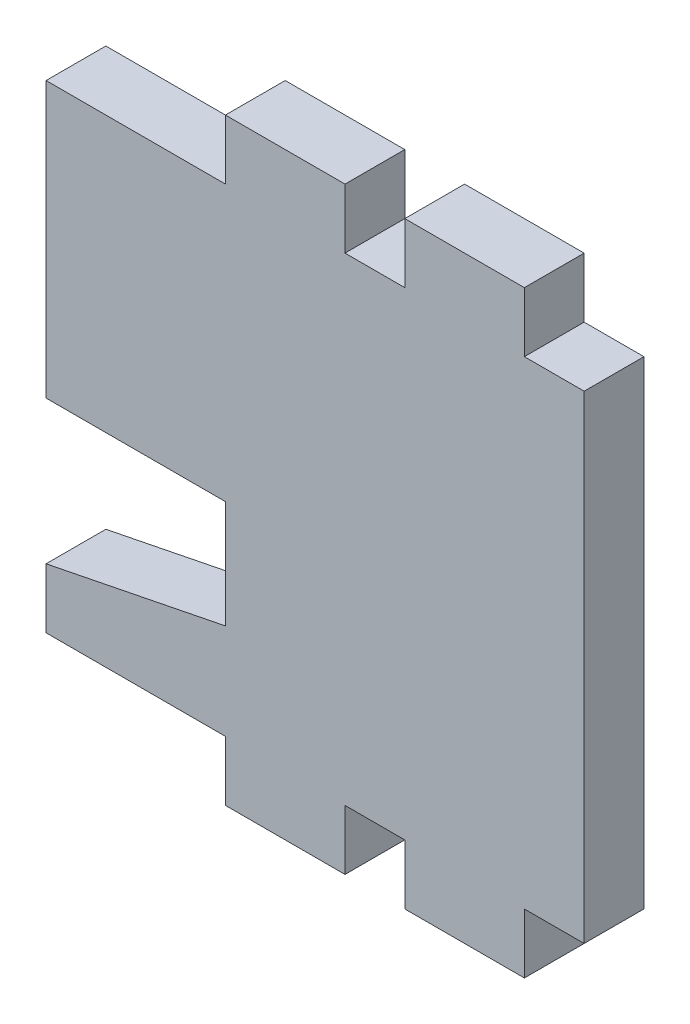
SolidWorks part; units mm, degrees
ref_plane "Plan de face" through (0, 0, 0) normal (0, 0, 1) x (1, 0, 0)
ref_plane "Plan de dessus" through (0, 0, 0) normal (0, 1, 0) x (1, 0, 0)
ref_plane "Plan de droite" through (0, 0, 0) normal (1, 0, 0) x (0, 0, -1)
sketch "Esquisse1" plane through (0, 0, 0) normal (0, 0, 1) x (1, 0, 0)
  line L0 (0, 20) -> (30, 20) construction
  line L1 (10, 0) -> (15, 0)
  line L2 (0, 0) -> (0, 40)
  line L3 (10, 40) -> (15, 40)
  line L4 (30, 0) -> (30, 40)
  line L5 (25, 40) -> (30, 40)
  line L6 (0, 40) -> (0, 45)
  line L7 (0, 45) -> (10, 45)
  line L8 (10, 40) -> (10, 45)
  line L9 (25, 0) -> (30, 0)
  line L10 (15, 40) -> (15, 45)
  line L11 (15, 45) -> (25, 45)
  line L12 (25, 40) -> (25, 45)
  line L13 (25, 0) -> (25, -5)
  line L14 (15, -5) -> (25, -5)
  line L15 (15, 0) -> (15, -5)
  line L16 (10, 0) -> (10, -5)
  line L17 (0, -5) -> (10, -5)
  line L18 (0, 0) -> (0, -5)
  dimension "D1" = 40
  dimension "D2" = 30
  dimension "D3" = 10
  dimension "D4" = 5
  dimension "D5" = 5
extrude "Boss.-Extru.1" add sketch "Esquisse1" along normal blind 5
sketch "Esquisse2" plane through (0, 0, 5) normal (0, 0, 1) x (1, 0, 0)
  line L0 (15, 40) -> (10, 40) construction
  line L1 (0, 0) -> (-15, 0)
  line L2 (0, 0) -> (0, 40)
  line L3 (0, 40) -> (-15, 40)
  line L4 (-15, 0) -> (-15, 5)
  line L5 (-15, 5) -> (0, 8)
  line L6 (0, 8) -> (0, 17)
  line L7 (0, 17) -> (-15, 17)
  line L8 (-15, 17) -> (-15, 40)
  line M1 (0, 45) -> (0, -5)
  dimension "D1" = 15
  dimension "D2" = 9
  dimension "D3" = 8
  dimension "D4" = 5
extrude "Boss.-Extru.2" add sketch "Esquisse2" against normal blind 5 contours L8 L7 L3 M1 | L5 L4 L1 L2 region at (-7.5, 28.5, 5) region at (-6.9231, 3.3077, 5)
